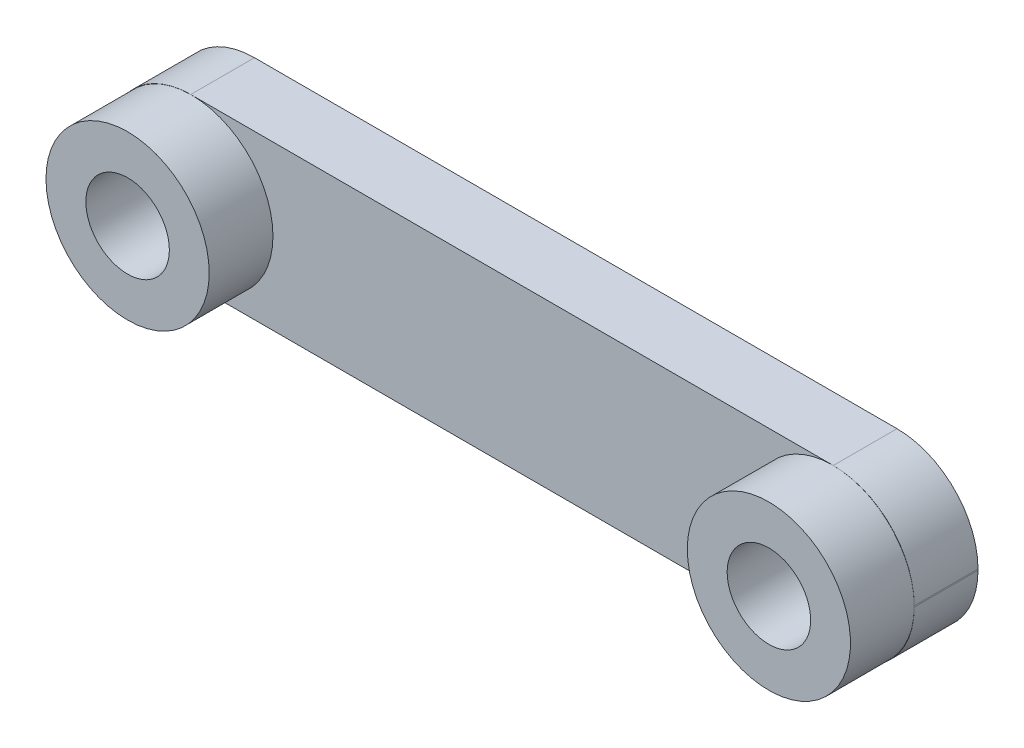
SolidWorks part; units mm, degrees
ref_plane "Front Plane" through (0, 0, 0) normal (0, 0, 1) x (1, 0, 0)
ref_plane "Top Plane" through (0, 0, 0) normal (0, 1, 0) x (1, 0, 0)
ref_plane "Right Plane" through (0, 0, 0) normal (1, 0, 0) x (0, 0, -1)
sketch "Sketch2" plane through (0, 0, 0) normal (0, 0, 1) x (1, 0, 0)
  line L1 (-63.095, 12.8) -> (63.095, 12.8)
  line L2 (-63.095, 12.8) -> (-63.095, -12.8)
  line L3 (-63.095, -12.8) -> (63.095, -12.8)
  line L4 (63.095, 12.8) -> (63.095, -12.8)
  line L5 (-63.095, 12.8) -> (63.095, -12.8) construction
  line L6 (-63.095, -12.8) -> (63.095, 12.8) construction
  point P0 (0, 0)
  dimension "D1" = 126.19
  dimension "D2" = 25.6
extrude "Boss-Extrude1" add sketch "Sketch2" along normal blind 10
sketch "Sketch3" plane through (0, 0, 10) normal (0, 0, 1) x (1, 0, 0)
  circle A0 centre (-50.296, 0) radius 12.8
  circle A1 centre (-50.296, 0) radius 6.55
  dimension "D1" = 25.6
  dimension "D3" = 13.1
  dimension "D2" = 50.296
extrude "Boss-Extrude2" add sketch "Sketch3" along normal blind 10
mirror "Mirror1" about plane through (0, 0, 0) normal (1, 0, 0) of "Boss-Extrude2"
fillet "Fillet2" radius 12.7 4 edges at (-63.095, -12.8, 5) (63.095, -12.8, 5) (63.095, 12.8, 5) (-63.095, 12.8, 5)
sketch "Sketch4" plane through (0, 0, 10) normal (0, 0, 1) x (1, 0, 0)
  circle A0 centre (-50.296, 0) radius 6.55
  circle A1 centre (-50.296, 0) radius 6.55 construction
  point P5 (0, 0)
extrude "Cut-Extrude1" cut sketch "Sketch4" against normal blind 5.6
mirror "Mirror2" about plane through (0, 0, 0) normal (1, 0, 0) of "Cut-Extrude1"
